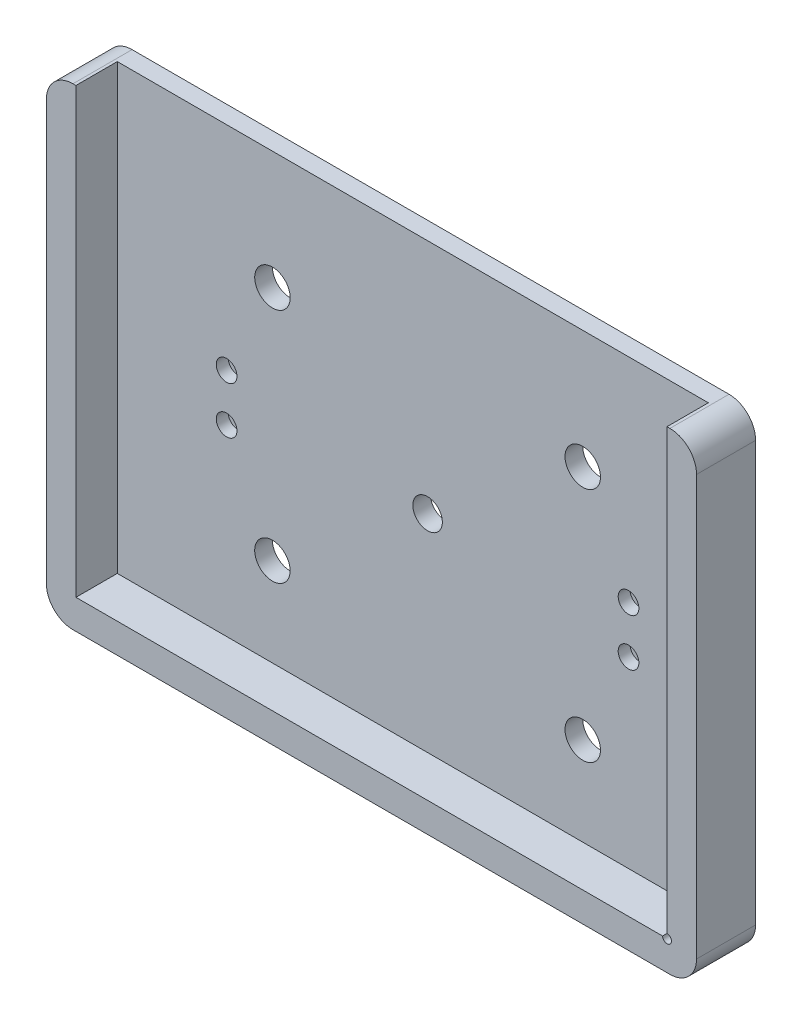
SolidWorks part; units mm, degrees
ref_plane "Plan de face" through (0, 0, 0) normal (0, 0, 1) x (1, 0, 0)
ref_plane "Plan de dessus" through (0, 0, 0) normal (0, 1, 0) x (1, 0, 0)
ref_plane "Plan de droite" through (0, 0, 0) normal (1, 0, 0) x (0, 0, -1)
sketch "Esquisse1" plane through (0, 0, 0) normal (0, 0, 1) x (1, 0, 0)
  line L1 (-71.7765, 70.7974) -> (128.2235, 70.7974)
  line L2 (-71.7765, 70.7974) -> (-71.7765, -79.2026)
  line L3 (-71.7765, -79.2026) -> (128.2235, -79.2026)
  line L4 (128.2235, 70.7974) -> (128.2235, -79.2026)
  dimension "D1" = 150
  dimension "D2" = 200
extrude "Boss.-Extru.1" add sketch "Esquisse1" along normal blind 6
sketch "Esquisse2" plane through (0, 0, 0) normal (0, 0, 1) x (1, 0, 0)
  line L0 (128.2235, 70.7974) -> (138.2235, 70.7974)
  line L1 (138.2235, 70.7974) -> (138.2235, -89.2026)
  line L2 (138.2235, -89.2026) -> (-81.7765, -89.2026)
  line L3 (-81.7765, -89.2026) -> (-81.7765, 70.7974)
  line L4 (-81.7765, 70.7974) -> (-71.7765, 70.7974)
extrude "Extru.-Mince1" add sketch "Esquisse2" along normal blind 20 thin
sketch "Esquisse3" plane through (0, 0, 0) normal (0, 0, 1) x (1, 0, 0)
  line L0 (-71.7765, -79.2026) -> (128.2235, -79.2026) construction
  line L1 (128.2235, -79.2026) -> (128.2235, 70.7974) construction
  line L2 (128.2235, 70.7974) -> (-71.7765, 70.7974) construction
  circle A0 centre (85.7235, -49.2026) radius 6
  circle A1 centre (-19.2894, -49.2124) radius 6
  circle A2 centre (85.7235, 30.7974) radius 6
  circle A3 centre (-19.2765, 30.8242) radius 6
  circle A4 centre (33.2134, -9.2026) radius 5
  dimension "D1" = 30
  dimension "D2" = 42.5
  dimension "D3" = 40
  dimension "D4" = 105
  dimension "D5" = 66.01
  dimension "D6" = 66.01
  dimension "D7" = 66.01
  dimension "D8" = 66.01
extrude "Enlèv. mat.-Extru.1" cut sketch "Esquisse3" along normal blind 20
shell "Coque1" thickness 2
sketch "Esquisse4" plane through (0, 0, 6) normal (0, 0, 1) x (1, 0, 0)
  line L0 (85.7235, 30.7974) -> (136.2235, 68.7974) construction
  line L1 (-19.2894, -49.2124) -> (85.7235, 30.7974) construction
ref_plane "Plan1" through (16.1944, -21.5215, 0) normal (-0.6013, 0.799, 0) x (0.799, 0.6013, 0)
sketch "Esquisse5" plane through (16.1944, -21.5215, 0) normal (-0.6013, 0.799, 0) x (0.799, 0.6013, 0)
  line L0 (95.0148, 0) -> (150.2149, 0)
rib "Nervure1" sketch "Esquisse5" sketch "Esquisse5" thickness 2 extrusion direction parallel to sketch draft on no parameters "D1"=2
sketch "Esquisse6" plane through (0, 0, 0) normal (0, 0, 1) x (1, 0, 0)
  line L0 (85.7235, -49.2026) -> (136.2235, -87.2026) construction
  line L1 (-19.2894, -49.2124) -> (85.7235, -49.2026) construction
ref_plane "Plan2" through (7.3518, 9.7702, 0) normal (0.6013, 0.799, 0) x (0.799, -0.6013, 0)
sketch "Esquisse7" plane through (7.3518, 9.7702, 0) normal (0.6013, 0.799, 0) x (0.799, -0.6013, 0)
  line L0 (106.0812, 0) -> (161.2812, 0)
rib "Nervure2" sketch "Esquisse7" sketch "Esquisse7" thickness 2 extrusion direction parallel to sketch draft on no parameters "D1"=2
sketch "Esquisse8" plane through (0, 0, 4) normal (0, 0, -1) x (-1, 0, 0)
  line L1 (19.2894, -49.2124) -> (79.7765, -87.2026) construction
ref_plane "Plan4" through (16.7086, -26.6031, 0) normal (0.5319, -0.8468, 0) x (-0.8468, -0.5319, 0)
sketch "Esquisse10" plane through (16.7086, -26.6031, 0) normal (0.5319, -0.8468, 0) x (-0.8468, -0.5319, 0)
  line L0 (50.5092, 0) -> (113.9371, 0)
rib "Nervure3" sketch "Esquisse10" sketch "Esquisse10" thickness 2 extrusion direction parallel to sketch draft on no parameters "D1"=2
sketch "Esquisse11" plane through (0, 0, 4) normal (0, 0, -1) x (-1, 0, 0)
  line L0 (19.2765, 30.8242) -> (79.7765, 68.7974) construction
ref_plane "Plan5" through (8.4314, 13.4331, 0) normal (-0.5316, -0.847, 0) x (-0.847, 0.5316, 0)
sketch "Esquisse12" plane through (8.4314, 13.4331, 0) normal (-0.5316, -0.847, 0) x (-0.847, 0.5316, 0)
  line L0 (40.7135, 0) -> (104.1433, 0)
rib "Nervure4" sketch "Esquisse12" sketch "Esquisse12" thickness 2 extrusion direction parallel to sketch draft on no parameters "D1"=2
sketch "Esquisse13" plane through (0, 0, 0) normal (0, 0, 1) x (1, 0, 0)
  circle A0 centre (101.2134, -17.2026) radius 5.5
  circle A1 centre (101.2134, -1.2026) radius 5.5
  circle A2 centre (-34.7866, -17.2026) radius 5.5
  circle A3 centre (-34.7866, -1.2026) radius 5.5
  point P9 (-34.7866, -9.2026)
  point P11 (101.2134, -9.2026)
  point P15 (33.2134, -9.2026)
extrude "Boss.-Extru.3" add sketch "Esquisse13" along normal up to surface (6 mm away) up to face at (-13.2765, 30.8242, 6)
sketch "Esquisse15" plane through (0, 0, 0) normal (0, 0, 1) x (1, 0, 0)
  circle A0 centre (-34.7866, -17.2026) radius 3.5
  circle A1 centre (-34.7866, -1.2026) radius 3.5
  circle A2 centre (101.2134, -17.2026) radius 3.5
  circle A3 centre (101.2134, -1.2026) radius 3.5
extrude "Enlèv. mat.-Extru.2" cut sketch "Esquisse15" against normal blind 4 from surface at 6 starting at face at (-13.2765, 30.8242, 6)
sketch "Esquisse16" plane through (0, 0, 0) normal (0, 0, 1) x (1, 0, 0)
  circle A0 centre (101.2134, -17.2026) radius 1.9
  circle A1 centre (101.2134, -1.2026) radius 1.9
  circle A2 centre (-34.7866, -1.2026) radius 1.9
  circle A3 centre (-34.7866, -17.2026) radius 1.9
extrude "Enlèv. mat.-Extru.3" cut sketch "Esquisse16" along normal through all
sketch "Esquisse17" plane through (0, 0, 4) normal (0, 0, -1) x (-1, 0, 0)
  line L0 (-101.2134, -1.2026) -> (-85.7235, 30.7974) construction
  line L1 (-101.2134, -17.2026) -> (-101.2134, -1.2026) construction
ref_plane "Plan6" through (81.5283, 39.4643, 0) normal (-0.9001, -0.4357, 0) x (-0.4357, 0.9001, 0)
sketch "Esquisse18" plane through (81.5283, 39.4643, 0) normal (-0.9001, -0.4357, 0) x (-0.4357, 0.9001, 0)
  line L0 (-17.6289, 0) -> (-39.6807, 0)
rib "Nervure5" sketch "Esquisse18" sketch "Esquisse18" thickness 2 extrusion direction parallel to sketch draft on no parameters "D1"=2
sketch "Esquisse21" plane through (0, 0, 0) normal (0, 0, 1) x (1, 0, 0)
  line L0 (101.2134, -17.2026) -> (85.7235, -49.2026) construction
ref_plane "Plan9" through (88.7462, -42.9582, 0) normal (0.9001, -0.4357, 0) x (-0.4357, -0.9001, 0)
sketch "Esquisse22" plane through (88.7462, -42.9582, 0) normal (0.9001, -0.4357, 0) x (-0.4357, -0.9001, 0)
  line L0 (-23.1143, 0) -> (-1.0625, 0)
rib "Nervure6" sketch "Esquisse22" sketch "Esquisse22" thickness 2 extrusion direction parallel to sketch draft on no parameters "D1"=2
ref_plane "Plan10" through (0.0046, -49.2106, 0) normal (-0.0001, 1, 0) x (1, 0.0001, 0)
sketch "Esquisse23" plane through (0.0046, -49.2106, 0) normal (-0.0001, 1, 0) x (1, 0.0001, 0)
  line L0 (77.7189, 0) -> (-11.294, 0)
rib "Nervure7" sketch "Esquisse23" sketch "Esquisse23" thickness 2 extrusion direction parallel to sketch draft on no parameters "D1"=2
ref_plane "Plan11" through (101.2134, 0, 0) normal (-1, 0, 0) x (0, 1, 0)
sketch "Esquisse24" plane through (101.2134, 0, 0) normal (-1, 0, 0) x (0, 1, 0)
  line L0 (-6.7026, 0) -> (-11.7026, 0)
rib "Nervure8" sketch "Esquisse24" sketch "Esquisse24" thickness 2 extrusion direction parallel to sketch draft on no parameters "D1"=2
sketch "Esquisse25" plane through (0, 0, 4) normal (0, 0, -1) x (-1, 0, 0)
  line L0 (-85.7235, -49.2026) -> (19.2765, 30.8242) construction
ref_plane "Plan12" through (7.7776, 10.2047, 0) normal (-0.6062, -0.7953, 0) x (-0.7953, 0.6062, 0)
sketch "Esquisse26" plane through (7.7776, 10.2047, 0) normal (-0.6062, -0.7953, 0) x (-0.7953, 0.6062, 0)
  line L0 (-90.0041, 0) -> (-38.994, 0)
rib "Nervure9" sketch "Esquisse26" sketch "Esquisse26" thickness 2 extrusion direction parallel to sketch draft on no parameters "D1"=2
sketch "Esquisse27" plane through (7.7776, 10.2047, 0) normal (-0.6062, -0.7953, 0) x (-0.7953, 0.6062, 0)
  line L0 (-24.9941, 0) -> (26.0159, 0)
rib "Nervure10" sketch "Esquisse27" sketch "Esquisse27" thickness 2 extrusion direction parallel to sketch draft on no parameters "D1"=2
ref_plane "Plan13" through (16.6389, -21.8385, 0) normal (-0.606, 0.7954, 0) x (0.7954, 0.606, 0)
sketch "Esquisse28" plane through (16.6389, -21.8385, 0) normal (-0.606, 0.7954, 0) x (0.7954, 0.606, 0)
  line L0 (78.8518, 0) -> (27.8418, 0)
rib "Nervure11" sketch "Esquisse28" sketch "Esquisse28" thickness 2 extrusion direction parallel to sketch draft on no parameters "D1"=2
sketch "Esquisse30" plane through (16.6389, -21.8385, 0) normal (-0.606, 0.7954, 0) x (0.7954, 0.606, 0)
  line L0 (13.8418, 0) -> (-37.1682, 0)
rib "Nervure12" sketch "Esquisse30" sketch "Esquisse30" thickness 2 extrusion direction parallel to sketch draft on no parameters "D1"=2
sketch "Esquisse31" plane through (0, 0, 4) normal (0, 0, -1) x (-1, 0, 0)
  line L0 (19.2894, -49.2124) -> (34.7866, -17.2026) construction
ref_plane "Plan14" through (-34.9282, -16.9102, 0) normal (-0.9001, -0.4358, 0) x (-0.4358, 0.9001, 0)
sketch "Esquisse32" plane through (-34.9282, -16.9102, 0) normal (-0.9001, -0.4358, 0) x (-0.4358, 0.9001, 0)
  line L0 (-5.8248, 0) -> (-27.8888, 0)
rib "Nervure13" sketch "Esquisse32" sketch "Esquisse32" thickness 2 extrusion direction parallel to sketch draft on no parameters "D1"=2
sketch "Esquisse33" plane through (0, 0, 4) normal (0, 0, -1) x (-1, 0, 0)
  line L0 (34.7866, -17.2026) -> (34.7866, -1.2026) construction
  line L1 (19.2765, 30.8242) -> (34.7866, -1.2026) construction
  line L2 (79.7765, 68.7974) -> (34.7866, -1.2026) construction
ref_plane "Plan15" through (-34.7866, 0, 0) normal (-1, 0, 0) x (0, 1, 0)
sketch "Esquisse34" plane through (-34.7866, 0, 0) normal (-1, 0, 0) x (0, 1, 0)
  line L0 (-6.7026, 0) -> (-11.7026, 0)
  line L1 (-11.7026, -4) -> (-11.7026, 0) construction
rib "Nervure14" sketch "Esquisse34" sketch "Esquisse34" thickness 2 extrusion direction parallel to sketch draft on no parameters "D1"=2
ref_plane "Plan16" through (-27.7062, 13.4178, 0) normal (0.9, -0.4359, 0) x (-0.4359, -0.9, 0)
sketch "Esquisse35" plane through (-27.7062, 13.4178, 0) normal (0.9, -0.4359, 0) x (-0.4359, -0.9, 0)
  line L0 (-11.3402, 0) -> (10.7446, 0)
rib "Nervure15" sketch "Esquisse35" sketch "Esquisse35" thickness 2 extrusion direction parallel to sketch draft on no parameters "D1"=2
sketch "Esquisse36" plane through (0, 0, 4) normal (0, 0, -1) x (-1, 0, 0)
  line L0 (19.2765, 30.8242) -> (-85.7235, 30.7974) construction
ref_plane "Plan17" through (0.0079, 30.8192, 0) normal (0.0003, 1, 0) x (1, -0.0003, 0)
sketch "Esquisse37" plane through (0.0079, 30.8192, 0) normal (0.0003, 1, 0) x (1, -0.0003, 0)
  line L0 (77.7157, 0) -> (-11.2843, 0)
rib "Nervure16" sketch "Esquisse37" sketch "Esquisse37" thickness 2 extrusion direction parallel to sketch draft on no parameters "D1"=2
ref_plane "Plan18" through (-25.1646, -16.1736, 0) normal (0.8412, 0.5407, 0) x (0.5407, -0.8412, 0)
sketch "Esquisse38" plane through (-25.1646, -16.1736, 0) normal (0.8412, 0.5407, 0) x (0.5407, -0.8412, 0)
  line L0 (-23.2965, 0) -> (-100.0143, 0)
rib "Nervure17" sketch "Esquisse38" sketch "Esquisse38" thickness 2 extrusion direction parallel to sketch draft on no parameters "D1"=2
sketch "Esquisse39" plane through (0, 0, 4) normal (0, 0, -1) x (-1, 0, 0)
  line L1 (34.7866, -17.2026) -> (79.7765, -87.2026) construction
ref_plane "Plan20" through (-16.7934, 10.7933, 0) normal (0.8412, -0.5407, 0) x (-0.5407, -0.8412, 0)
sketch "Esquisse41" plane through (-16.7934, 10.7933, 0) normal (0.8412, -0.5407, 0) x (-0.5407, -0.8412, 0)
  line L0 (38.7795, 0) -> (119.2544, 0)
rib "Nervure19" sketch "Esquisse41" sketch "Esquisse41" thickness 2 extrusion direction parallel to sketch draft on no parameters "D1"=2
sketch "Esquisse42" plane through (0, 0, 4) normal (0, 0, -1) x (-1, 0, 0)
  line L0 (-101.2134, -1.2026) -> (-136.2235, 68.7974) construction
ref_plane "Plan21" through (81.4424, -40.733, 0) normal (-0.8944, 0.4473, 0) x (0.4473, 0.8944, 0)
sketch "Esquisse43" plane through (81.4424, -40.733, 0) normal (-0.8944, 0.4473, 0) x (0.4473, 0.8944, 0)
  line L0 (125.1493, 0) -> (49.699, 0)
rib "Nervure20" sketch "Esquisse43" sketch "Esquisse43" thickness 2 extrusion direction parallel to sketch draft on no parameters "D1"=2
sketch "Esquisse44" plane through (0, 0, 4) normal (0, 0, -1) x (-1, 0, 0)
  line L0 (-101.2134, -17.2026) -> (-136.2235, -87.2026) construction
ref_plane "Plan22" through (74.079, 37.0503, 0) normal (0.8944, 0.4473, 0) x (0.4473, -0.8944, 0)
sketch "Esquisse45" plane through (74.079, 37.0503, 0) normal (0.8944, 0.4473, 0) x (0.4473, -0.8944, 0)
  line L0 (66.1601, 0) -> (141.6104, 0)
rib "Nervure21" sketch "Esquisse45" sketch "Esquisse45" thickness 2 extrusion direction parallel to sketch draft on no parameters "D1"=2
fillet "Congé1" radius 1.75 1 edges at (-79.7765, 66.9479, 9)
fillet "Congé2" radius 1.75 1 edges at (-76.512, 65.5678, 9)
fillet "Congé3" radius 1.75 1 edges at (-77.8954, 68.7974, 9)
fillet "Congé4" radius 1.75 1 edges at (-79.7765, -85.353, 9)
fillet "Congé5" radius 1.75 1 edges at (-76.5103, -83.9704, 9)
fillet "Congé6" radius 1.75 1 edges at (-77.8963, -87.2026, 9)
fillet "Congé8" radius 1.75 1 edges at (134.5604, -87.2026, 9)
fillet "Congé9" radius 1.75 1 edges at (133.4271, -83.8468, 9)
fillet "Congé10" radius 1.75 1 edges at (136.2235, -84.967, 9)
fillet "Congé13" radius 1.75 1 edges at (134.5604, 68.7974, 9)
fillet "Congé14" radius 1.75 1 edges at (133.4271, 65.4417, 9)
fillet "Congé15" radius 1.75 1 edges at (136.2235, 66.5619, 9)
fillet "Congé16" radius 1.75 1 edges at (104.527, 3.1872, 2)
fillet "Congé17" radius 1.75 1 edges at (102.7382, 4.0818, 2)
fillet "Congé18" radius 1.75 1 edges at (99.7571, 4.1011, 2)
fillet "Congé19" radius 1.75 1 edges at (97.9569, 3.2297, 2)
fillet "Congé20" radius 1.75 1 edges at (100.2134, -6.6109, 2)
fillet "Congé21" radius 1.75 1 edges at (102.2134, -6.6109, 2)
fillet "Congé22" radius 1.75 1 edges at (102.2134, -11.7943, 2)
fillet "Congé23" radius 1.75 1 edges at (104.527, -21.5923, 2)
fillet "Congé24" radius 1.75 1 edges at (102.7382, -22.487, 2)
fillet "Congé25" radius 1.75 1 edges at (97.9569, -21.6349, 2)
fillet "Congé26" radius 1.75 1 edges at (100.2134, -11.7943, 2)
fillet "Congé27" radius 1.75 1 edges at (99.7571, -22.5063, 2)
fillet "Congé28" radius 1.75 1 edges at (90.0819, -42.494, 2)
fillet "Congé29" radius 1.75 1 edges at (92.6671, -53.1759, 2)
fillet "Congé30" radius 1.75 1 edges at (91.4645, -54.774, 2)
fillet "Congé31" radius 1.75 1 edges at (77.7864, -50.2033, 2)
fillet "Congé32" radius 1.75 1 edges at (77.7862, -48.2033, 2)
fillet "Congé33" radius 1.75 1 edges at (78.8046, -45.1866, 2)
fillet "Congé34" radius 1.75 1 edges at (80.0169, -43.5959, 2)
fillet "Congé35" radius 1.75 1 edges at (-11.352, -50.2117, 2)
fillet "Congé36" radius 1.75 1 edges at (-25.479, -54.2808, 2)
fillet "Congé37" radius 1.75 1 edges at (-26.5427, -52.5872, 2)
fillet "Congé38" radius 1.75 1 edges at (-23.6481, -42.5041, 2)
fillet "Congé39" radius 1.75 1 edges at (-33.33, -22.5062, 2)
fillet "Congé40" radius 1.75 1 edges at (-36.8695, -22.2929, 2)
fillet "Congé41" radius 1.75 1 edges at (-38.552, -21.2116, 2)
fillet "Congé42" radius 1.75 1 edges at (-35.7866, -11.7943, 2)
fillet "Congé43" radius 1.75 1 edges at (-31.5299, -21.6347, 2)
fillet "Congé44" radius 1.75 1 edges at (-33.7866, -11.7943, 2)
fillet "Congé45" radius 1.75 1 edges at (-33.7866, -6.6109, 2)
fillet "Congé46" radius 1.75 1 edges at (-31.5293, 3.2291, 2)
fillet "Congé47" radius 1.75 1 edges at (-21.836, 23.2447, 2)
fillet "Congé48" radius 1.75 1 edges at (-13.5699, 25.2175, 2)
fillet "Congé49" radius 1.75 2 edges at (27.0994, -12.6114, 2) (27.1052, -5.7834, 2)
fillet "Congé50" radius 1.75 17 edges at (77.7865, 31.7994, 2) (91.4645, 36.3689, 2) (92.6671, 34.7708, 2) (28.3129, -14.2012, 2) (38.1295, -14.1857, 2) (39.338, -12.5921, 2) (39.3333, -5.8047, 2) (28.3214, -4.1957, 2) (38.1227, -4.2127, 2) (78.804, 26.7825, 2) (77.786, 29.7994, 2) (80.016, 25.1917, 2) (88.2817, 23.2174, 2) (-12.3698, -45.1975, 2) (-11.3522, -48.2117, 2) (-21.848, -41.6326, 2) (-13.5819, -43.6067, 2)
fillet "Congé51" radius 1.75 8 edges at (-38.552, 2.8064, 2) (-35.7866, -6.6109, 2) (-36.8695, 3.8878, 2) (-33.3294, 4.1008, 2) (-23.636, 24.1164, 2) (-26.5308, 34.1967, 2) (-25.4676, 35.8907, 2) (-11.3389, 31.8221, 2)
fillet "Congé52" radius 1.75 6 edges at (130.2235, 54.5654, 11) (130.2235, -72.9705, 11) (126.5867, -81.2026, 11) (-68.3432, -81.2026, 11) (-73.7765, -76.0176, 11) (-73.7765, 57.6124, 11)
fillet "Congé53" radius 9 1 edges at (138.2235, 70.7974, 10)
fillet "Congé54" radius 9 3 edges at (-81.7765, 70.7974, 10) (-81.7765, -89.2026, 10) (138.2235, -89.2026, 10)
sketch "Esquisse46" plane through (0, 0, 6) normal (0, 0, 1) x (1, 0, 0)
  circle A0 centre (128.2235, -79.2026) radius 1.5
extrude "Enlèv. mat.-Extru.4" cut sketch "Esquisse46" along normal through all
